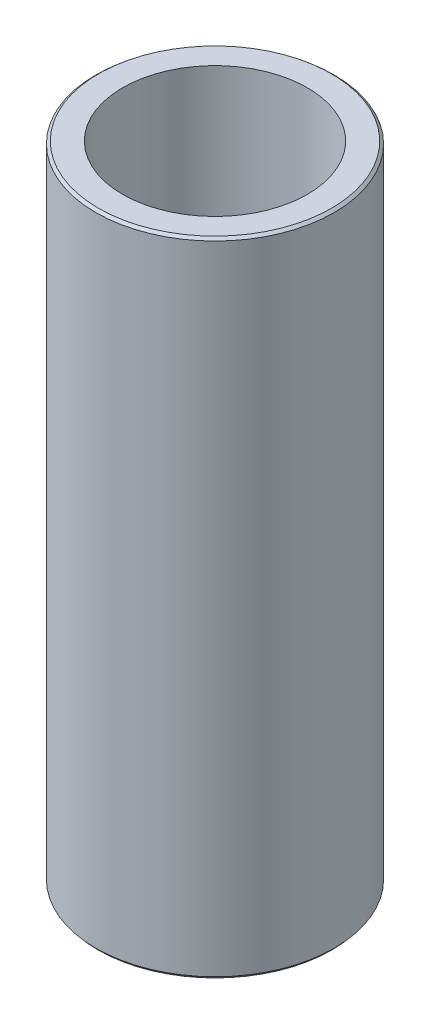
SolidWorks part; units mm, degrees
ref_plane "Front Plane" through (0, 0, 0) normal (0, 0, 1) x (1, 0, 0)
ref_plane "Top Plane" through (0, 0, 0) normal (0, 1, 0) x (1, 0, 0)
ref_plane "Right Plane" through (0, 0, 0) normal (1, 0, 0) x (0, 0, -1)
sketch "Sketch1" plane through (0, 0, 0) normal (0, 1, 0) x (1, 0, 0)
  circle A0 centre (0, 0) radius 40
  dimension "SHAFT_OD" = 80
extrude "Boss-Extrude1" add sketch "Sketch1" along normal blind 215.4803
sketch "Sketch2" plane through (0, 0, 0) normal (0, 1, 0) x (1, 0, 0)
  circle A0 centre (0, 0) radius 31.0071
  dimension "BORE_D" = 62.0143
extrude "Cut-Extrude1" cut sketch "Sketch2" along normal through all
chamfer "Chamfer1" distance 0.7827 angle 49.479 2 edges at (0, 215.4803, 40) (0, 0, 40) first distance on face at (0, 215.4803, 40) first distance on face at (0, 0, 31.0071)
